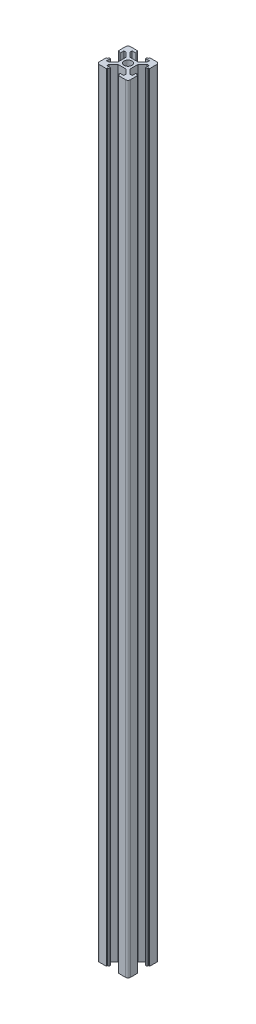
SolidWorks part; units mm, degrees
material "6063-O"
ref_plane "Front Plane" through (0, 0, 0) normal (0, 0, 1) x (1, 0, 0)
ref_plane "Top Plane" through (0, 0, 0) normal (0, 1, 0) x (1, 0, 0)
ref_plane "Right Plane" through (0, 0, 0) normal (1, 0, 0) x (0, 0, -1)
sketch "Sketch1" plane through (0, 0, 0) normal (0, 1, 0) x (1, 0, 0)
  line L0 (0, 14.5399) -> (0, 10) construction
  line L1 (-16.8658, 0) -> (2.5, 0) construction
  line L2 (13.2784, 3.9) -> (3.9, 3.9) construction
  line L3 (0, 0) -> (2.5, 0)
  line L4 (0, 0) -> (0, 2.5)
  line L5 (3.9, 10) -> (8.5, 10)
  line L6 (9.2, 0) -> (16.4291, 0) construction
  line L7 (-2.63, 3.9) -> (2.63, 3.9)
  line L9 (2.5491, 3.9) -> (2.63, 3.9)
  line L10 (3.9, 0) -> (3.9, 2.63)
  line L11 (13.2784, 3.1) -> (2.5491, 3.1) construction
  line L12 (8.2, 7.5573) -> (8.2, -3.0868) construction
  line L13 (9.2, 7.2593) -> (9.2, -8.1534) construction
  line L14 (10, 3.9) -> (9.2, 3.9)
  line L15 (9.2, 3.9) -> (9.2, 3.1)
  line L16 (9.2, 3.1) -> (8.2, 3.1)
  line L17 (8.2, 3.1) -> (8.2, 5.5)
  line L18 (8.2, 5.5) -> (6.77, 5.5)
  line L19 (6.77, 5.5) -> (3.9, 2.63)
  line L20 (5.0973, 5.5) -> (13.0082, 5.5) construction
  line L21 (3.1, 11.2046) -> (3.1, 2.6994) construction
  line L22 (3.9, 10.7498) -> (3.9, 3.9) construction
  line L23 (5.5, 11.523) -> (5.5, 1.4941) construction
  line L24 (-2.2597, 8.2) -> (6.1545, 8.2) construction
  line L25 (-2.9419, 9.2) -> (5.7225, 9.2) construction
  line L26 (3.9, 10) -> (3.9, 9.2)
  line L27 (3.9, 9.2) -> (3.1, 9.2)
  line L28 (3.1, 9.2) -> (3.1, 8.2)
  line L29 (3.1, 8.2) -> (5.5, 8.2)
  line L30 (5.5, 8.2) -> (5.5, 6.77)
  line L31 (5.5, 6.77) -> (2.63, 3.9)
  line L32 (0, 2.5) -> (0, -14.4122) construction
  line L33 (10, 3.9) -> (10, 8.5)
  line L34 (9.2, 0) -> (10, 0)
  line L35 (2.63, 3.9) -> (2.5491, 3.9) construction
  line L36 (3.9, 2.63) -> (3.9, 2.0627) construction
  line L37 (10, -3.9) -> (10, -8.5)
  line L38 (3.9, -10) -> (8.5, -10)
  line L39 (3.9, -10) -> (3.9, -9.2)
  line L40 (3.9, -9.2) -> (3.1, -9.2)
  line L41 (3.1, -9.2) -> (3.1, -8.2)
  line L42 (3.1, -8.2) -> (5.5, -8.2)
  line L43 (5.5, -8.2) -> (5.5, -6.77)
  line L44 (5.5, -6.77) -> (2.63, -3.9)
  line L45 (0, -3.9) -> (2.63, -3.9)
  line L46 (3.9, 0) -> (3.9, -2.63)
  line L47 (6.77, -5.5) -> (3.9, -2.63)
  line L48 (8.2, -5.5) -> (6.77, -5.5)
  line L49 (8.2, -3.1) -> (8.2, -5.5)
  line L50 (9.2, -3.1) -> (8.2, -3.1)
  line L51 (9.2, -3.9) -> (9.2, -3.1)
  line L52 (10, -3.9) -> (9.2, -3.9)
  line L53 (-3.9, -10) -> (-8.5, -10)
  line L54 (-10, -3.9) -> (-10, -8.5)
  line L55 (-10, -3.9) -> (-9.2, -3.9)
  line L56 (-9.2, -3.9) -> (-9.2, -3.1)
  line L57 (-9.2, -3.1) -> (-8.2, -3.1)
  line L58 (-8.2, -3.1) -> (-8.2, -5.5)
  line L59 (-8.2, -5.5) -> (-6.77, -5.5)
  line L60 (-6.77, -5.5) -> (-3.9, -2.63)
  line L61 (-3.9, 0) -> (-3.9, -2.63)
  line L62 (0, -3.9) -> (-2.63, -3.9)
  line L63 (-5.5, -6.77) -> (-2.63, -3.9)
  line L64 (-5.5, -8.2) -> (-5.5, -6.77)
  line L65 (-3.1, -8.2) -> (-5.5, -8.2)
  line L66 (-3.1, -9.2) -> (-3.1, -8.2)
  line L67 (-3.9, -9.2) -> (-3.1, -9.2)
  line L68 (-3.9, -10) -> (-3.9, -9.2)
  line L69 (-10, 3.9) -> (-10, 8.5)
  line L70 (-3.9, 10) -> (-8.5, 10)
  line L71 (-3.9, 10) -> (-3.9, 9.2)
  line L72 (-3.9, 9.2) -> (-3.1, 9.2)
  line L73 (-3.1, 9.2) -> (-3.1, 8.2)
  line L74 (-3.1, 8.2) -> (-5.5, 8.2)
  line L75 (-5.5, 8.2) -> (-5.5, 6.77)
  line L76 (-5.5, 6.77) -> (-2.63, 3.9)
  line L78 (-3.9, 0) -> (-3.9, 2.63)
  line L79 (-6.77, 5.5) -> (-3.9, 2.63)
  line L80 (-8.2, 5.5) -> (-6.77, 5.5)
  line L81 (-8.2, 3.1) -> (-8.2, 5.5)
  line L82 (-9.2, 3.1) -> (-8.2, 3.1)
  line L83 (-9.2, 3.9) -> (-9.2, 3.1)
  line L84 (-10, 3.9) -> (-9.2, 3.9)
  line L85 (0, 3.9) -> (-2.63, 3.9) [skipped]
  circle A0 centre (0, 0) radius 2.5
  arc A1 (8.5, 10) -> (10, 8.5) centre (8.5, 8.5) cw
  arc A2 (10, -8.5) -> (8.5, -10) centre (8.5, -8.5) cw
  arc A4 (-8.5, -10) -> (-10, -8.5) centre (-8.5, -8.5) cw
  arc A6 (-10, 8.5) -> (-8.5, 10) centre (-8.5, 8.5) cw
  point P12 (10, 10)
  point P126 (0, 0)
  dimension "D3" = 5
  dimension "D4" = 1.5
  dimension "D1" = 10
  dimension "D2" = 10
  dimension "D6" = 3.9
  dimension "D7" = 3.9
  dimension "D8" = 3.1
  dimension "D9" = 4
  dimension "D11" = 5.5
  dimension "D12" = 1.8
  dimension "D13" = 0.8
  dimension "D14" = 3.9
  dimension "D15" = 3.1
  dimension "D16" = 5.5
  dimension "D17" = 1.27
  dimension "D18" = 1.27
  dimension "D19" = 1.27
  dimension "D20" = 1.27
extrude "Boss-Extrude1" add sketch "Sketch1" along normal blind 500 contours A6 L69 L84 L83 L82 L81 L80 L79 L78 L61 L60 L59 L58 L57 L56 L55 L54 A4 L53 L68 L67 L66 L65 L64 L63 L62 L45 L44 L43 L42 L41 L40 L39 L38 A2 L37 L52 L51 L50 L49 L48 L47 L46 L10 L19 L18 L17 L16 L15 L14 L33 region at (6.2, 0, -9.7172)
